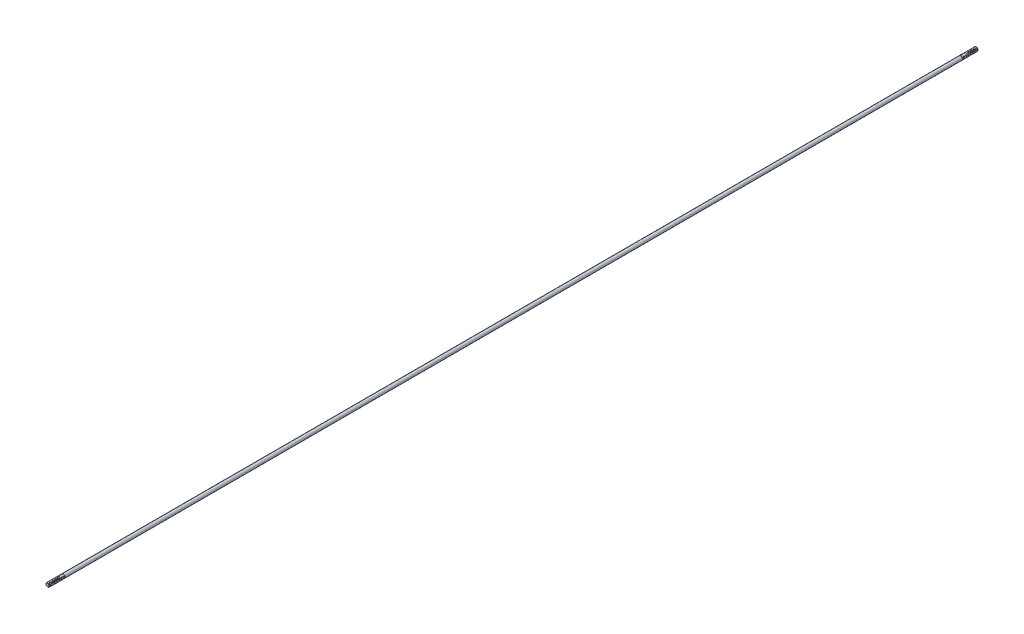
SolidWorks part; units mm, degrees
material "AISI 304"
ref_plane "Front Plane" through (0, 0, 0) normal (0, 0, 1) x (1, 0, 0)
ref_plane "Top Plane" through (0, 0, 0) normal (0, 1, 0) x (1, 0, 0)
ref_plane "Right Plane" through (0, 0, 0) normal (1, 0, 0) x (0, 0, -1)
sketch "Sketch1" plane through (0, 0, 0) normal (0, 0, 1) x (1, 0, 0)
  circle A0 centre (0, 0) radius 4.7625
  dimension "D1" = 9.525
extrude "Boss-Extrude1" add sketch "Sketch1" along normal mid plane 2280
chamfer "Chamfer1" distance 1 angle 45 2 edges at (4.7625, 0, -1140) (4.7625, 0, 1140)
thread "Thread1" pitch 1.5875 method cut profile "Thread Profile1" start angle 0, offset 2, length 40, pitch 1.5875, diameter 9.525
ref_plane "Plane1" through (-4.7625, 0, 1142) normal (0, -1, 0) x (-1, 0, 0)
sketch "Thread Profile1" plane through (-4.7625, 0, 1142) normal (0, -1, 0) x (-1, 0, 0)
  line L0 (0, 0) -> (0, 1.5875) construction
  line L11 (0, 0) -> (0, 1.3891)
  line L12 (0, 1.3891) -> (-0.8593, 0.893)
  line L13 (-0.8593, 0.893) -> (-0.8593, 0.4961)
  line L15 (-0.8593, 0.4961) -> (0, 0)
  line L17 (-0.8593, 0.6945) -> (0, 0.6945) construction
  point P2 (0, 0)
  dimension "Pitch" = 1.5875
  dimension "Profile_Angle" = 60
  dimension "Profile_Land" = 0.3969
  dimension "Profile_Height" = 0.8593
thread "Thread2" pitch 1.5875 method cut profile "Thread Profile2" start angle 0, offset 2, length 40, pitch 1.5875, diameter 9.525
ref_plane "Plane2" through (4.7625, 0, -1142) normal (0, -1, 0) x (1, 0, 0)
sketch "Thread Profile2" plane through (4.7625, 0, -1142) normal (0, -1, 0) x (1, 0, 0)
  line L0 (0, 0) -> (0, 1.5875) construction
  line L11 (0, 0) -> (0, 1.3891)
  line L12 (0, 1.3891) -> (-0.8593, 0.893)
  line L13 (-0.8593, 0.893) -> (-0.8593, 0.4961)
  line L15 (-0.8593, 0.4961) -> (0, 0)
  line L17 (-0.8593, 0.6945) -> (0, 0.6945) construction
  point P2 (0, 0)
  dimension "Pitch" = 1.5875
  dimension "Profile_Angle" = 60
  dimension "Profile_Land" = 0.3969
  dimension "Profile_Height" = 0.8593
